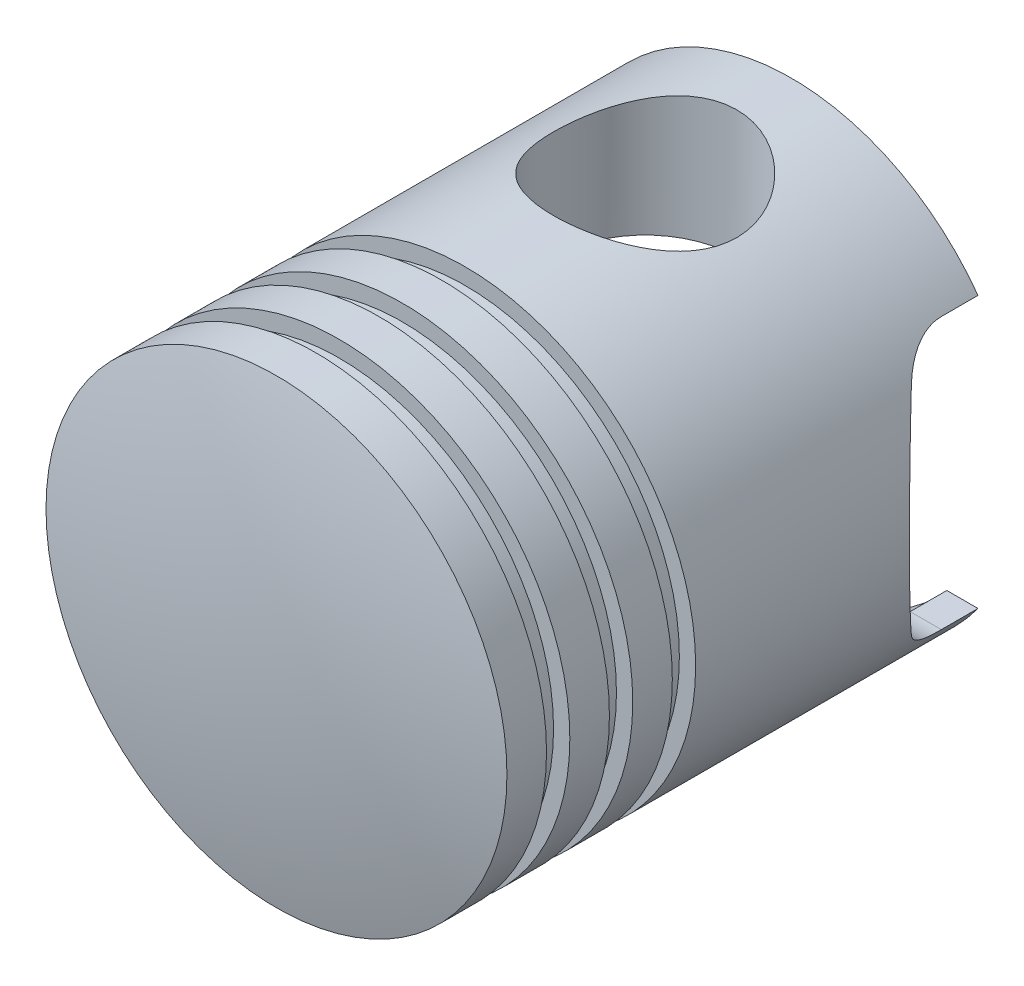
SolidWorks part; units mm, degrees
ref_plane "Front Plane" through (0, 0, 0) normal (0, 0, 1) x (1, 0, 0)
ref_plane "Top Plane" through (0, 0, 0) normal (0, 1, 0) x (1, 0, 0)
ref_plane "Right Plane" through (0, 0, 0) normal (1, 0, 0) x (0, 0, -1)
sketch "Sketch1" plane through (0, 0, 0) normal (0, 0, 1) x (1, 0, 0)
  circle A0 centre (0, 0) radius 42.5
  dimension "D1" = 85
extrude "Boss-Extrude1" add sketch "Sketch1" along normal blind 95 contours A0
sketch "Sketch2" plane through (0, 0, 95) normal (0, 0, 1) x (1, 0, 0)
  circle A0 centre (0, 0) radius 39.5
  dimension "D1" = 79
extrude "Cut-Extrude1" cut sketch "Sketch2" against normal blind 4.3 from offset 7.3 flip side to cut offset against normal yes
pattern_linear "LPattern1" count 3 spacing 11.6 along (0, 0, -1) of "Cut-Extrude1"
sketch "Sketch3" plane through (0, 0, 0) normal (0, 0, -1) x (-1, 0, 0)
  circle A0 centre (0, 0) radius 38
  dimension "D1" = 76
extrude "Cut-Extrude2" cut sketch "Sketch3" against normal blind 85
dome "Dome1" faces to dome 1 distance 5 reverse direction no elliptical dome no face at (42.5, 0, 95) parameters "D1"=5
sketch "Sketch5" plane through (0, 0, 0) normal (0, 1, 0) x (1, 0, 0)
  line L0 (38, 0) -> (-38, 0) construction
  circle A0 centre (0, -27) radius 16.9
  dimension "D1" = 33.8
  dimension "D2" = 27
extrude "Cut-Extrude3" cut sketch "Sketch5" against normal through all both and the other way through all
sketch "Sketch7" plane through (0, 0, 0) normal (1, 0, 0) x (0, 0, -1)
  line L1 (0, 25) -> (0, 0)
  line L3 (0, 0) -> (0, -25)
  line L4 (0, 25) -> (-12, 25)
  line L5 (0, -25) -> (-12, -25)
  arc A0 (-12, 25) -> (-12, -25) centre (19.225, 0) ccw
  dimension "D3" = 40
  dimension "D1" = 25
  dimension "D2" = 12
extrude "Cut-Extrude4" cut sketch "Sketch7" against normal through all both and the other way through all
fillet "Fillet1" radius 10 4 edges at (31.4937, 25, 12) (31.4937, -25, 12) (-31.4937, -25, 12) (-31.4937, 25, 12)
sketch "Sketch8" plane through (0, 0, 0) normal (0, 1, 0) x (1, 0, 0)
  circle A0 centre (0, -27) radius 16.9
  circle A1 centre (0, -27) radius 22.5
  dimension "D1" = 45
extrude "Boss-Extrude3" add sketch "Sketch8" along normal up to next from offset 19
mirror "Mirror1" about plane through (0, 0, 0) normal (0, 1, 0) of "Boss-Extrude3"
